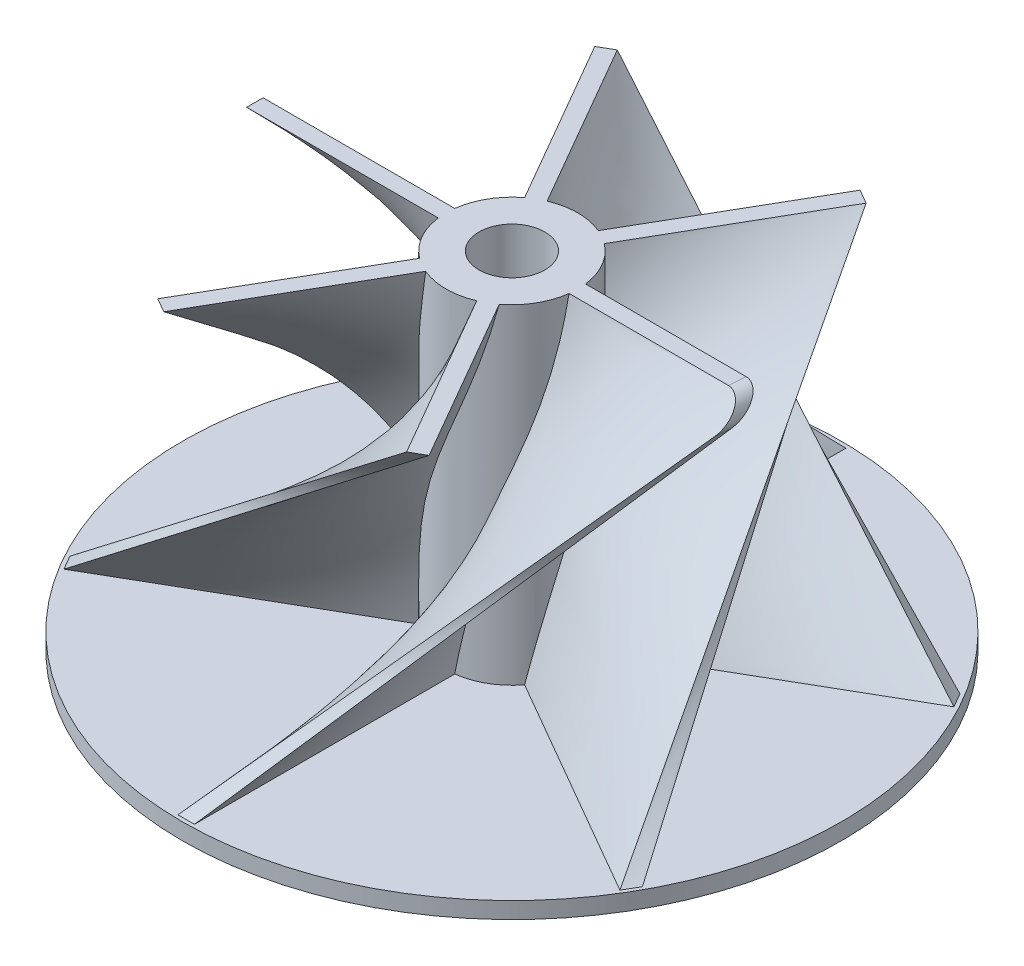
SolidWorks part; units mm, degrees
ref_plane "Front Plane" through (0, 0, 0) normal (0, 0, 1) x (1, 0, 0)
ref_plane "Top Plane" through (0, 0, 0) normal (0, 1, 0) x (1, 0, 0)
ref_plane "Right Plane" through (0, 0, 0) normal (1, 0, 0) x (0, 0, -1)
sketch "Sketch1" plane through (0, 0, 0) normal (0, 1, 0) x (1, 0, 0)
  line L0 (0, 0) -> (0, 49429.2201) construction
  line L1 (0, 0) -> (-49429.2201, 0) construction
  circle A0 centre (0, 0) radius 100
  circle A1 centre (0, 0) radius 20
  circle A2 centre (0, 0) radius 10
  dimension "D1" = 200
  dimension "D2" = 20
  dimension "D3" = 40
extrude "Boss-Extrude1" add sketch "Sketch1" along normal blind 5 contours A0 A1 region at (-97.1716, 0, 0)
extrude "Boss-Extrude2" add sketch "Sketch1<3>" along normal blind 105 contours A1 A2 region at (-19.4343, 0, 0)
sketch "Sketch1<3>" plane through (0, 0, 0) normal (0, 1, 0) x (1, 0, 0) same geometry as "Sketch1"
ref_plane "Plane1" through (0, 105, 0) normal (0, 1, 0) x (1, 0, 0)
sketch "Sketch2" plane through (0, 105, 0) normal (0, 1, 0) x (1, 0, 0)
  line L0 (78, 2.5) -> (78, -2.5)
  line L1 (78, -2.5) -> (19.8431, -2.5)
  line L3 (19.8431, 2.5) -> (78, 2.5)
  arc A1 (19.8431, -2.5) -> (19.8431, 2.5) centre (0, 0) ccw
  dimension "D2" = 5
sketch "Sketch4" plane through (0, 5, 0) normal (0, 1, 0) x (1, 0, 0)
  line L0 (-2.5, -19.8431) -> (-2.5, -98.8431)
  line L1 (-2.5, -98.8431) -> (2.5, -98.8431)
  line L2 (2.5, -98.8431) -> (2.5, -19.8431)
  arc A0 (-2.5, -19.8431) -> (2.5, -19.8431) centre (0, 0) ccw
  point P2 (0, -98.8431)
  dimension "D4" = 40
  dimension "D1" = 79
  dimension "D2" = 5
  dimension "D3" = 0
loft "Loft1" add profiles "Sketch4", "Sketch2" connector at (-2.5, 5, 19.8431) connector at (19.8431, 105, 2.5)
fillet "Fillet1" radius 5 1 edges
ref_axis "Axis1" through (0, 105, 0) along (0, -1, 0)
pattern_circular "CirPattern1" count 6 every 60 about axis through (0, 105, 0) along (0, -1, 0) of "Loft1"
